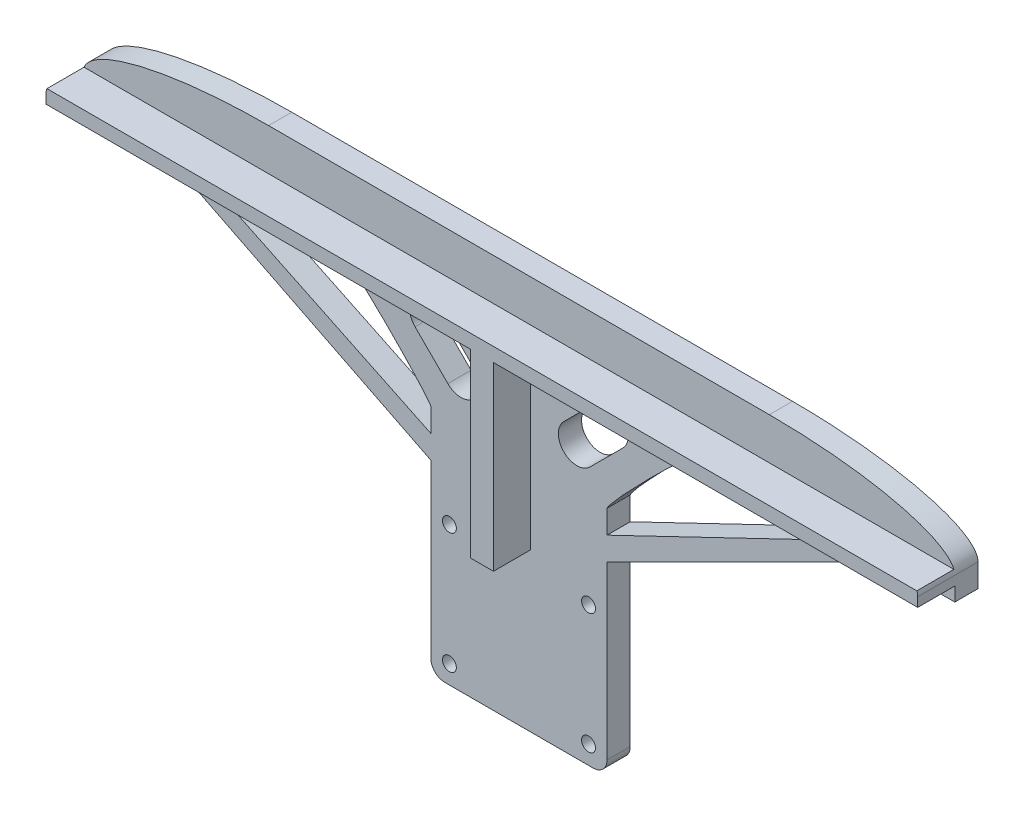
SolidWorks part; units mm, degrees
ref_plane "Front" through (0, 0, 0) normal (0, 0, 1) x (1, 0, 0)
ref_plane "Top" through (0, 0, 0) normal (0, 1, 0) x (1, 0, 0)
ref_plane "Right" through (0, 0, 0) normal (1, 0, 0) x (0, 0, -1)
sketch "Sketch1" plane through (0, 0, 0) normal (0, 0, 1) x (1, 0, 0)
  line L0 (38, 0) -> (113, 0)
  line L1 (0, 0) -> (38, 0)
  line L2 (0, 0) -> (0, -70)
  line L3 (0, -70) -> (38, -70)
  line L4 (38, 0) -> (38, -70)
  line L5 (113, 0) -> (113, 15)
  line L6 (113, 15) -> (-75, 15)
  line L7 (-75, 15) -> (-75, 0)
  line L8 (-75, 0) -> (0, 0)
  dimension "D1" = 38
  dimension "D2" = 70
  dimension "D3" = 75
  dimension "D4" = 75
  dimension "D5" = 15
extrude "Boss-Extrude1" add sketch "Sketch1" along normal blind 5 contours L4 L1 L2 L3 | L7 L8 L1 L0 L5 L6 region at (19, 7.5, 0) region at (19, -35, 0)
sketch "Sketch2" plane through (0, 0, 5) normal (0, 0, 1) x (1, 0, 0)
  line L0 (38, 0) -> (38, -70) construction
  line L1 (0, -70) -> (38, -70) construction
  circle A0 centre (34, -66) radius 1.5
  circle A1 centre (4, -66) radius 1.5
  circle A2 centre (4, -40) radius 1.5
  circle A3 centre (34, -40) radius 1.5
  dimension "D1" = 3
  dimension "D2" = 4
  dimension "D3" = 4
  dimension "D4" = 2
  dimension "D5" = 2
extrude "Cut-Extrude1" cut sketch "Sketch2" against normal through all
fillet "Fillet1" radius 3 2 edges at (38, -70, 2.5) (0, -70, 2.5)
fillet "Fillet2" radius 20 2 edges at (0, 0, 2.5) (38, 0, 2.5) conic rho 0.05
sketch "Sketch3" plane through (0, 0, 5) normal (0, 0, 1) x (1, 0, 0)
  line L0 (-75, 15) -> (-75, 0) construction
  line L1 (-75, 3) -> (113, 3)
  line L2 (-75, 3) -> (-75, 6)
  line L3 (-75, 6) -> (113, 6)
  line L4 (113, 3) -> (113, 6)
  line L5 (113, 0) -> (113, 15) construction
  dimension "D1" = 3
  dimension "D2" = 12
extrude "Boss-Extrude2" add sketch "Sketch3" along normal blind 8
sketch "Sketch4" plane through (0, 0, 5) normal (0, 0, 1) x (1, 0, 0)
  line L0 (-75, 3) -> (113, 3) construction
  line L1 (16.5, 3) -> (21.5, 3)
  line L2 (16.5, 3) -> (16.5, -36)
  line L3 (16.5, -36) -> (21.5, -36)
  line L4 (21.5, 3) -> (21.5, -36)
  line L5 (0, -20) -> (0, -67) construction
  dimension "D1" = 39
  dimension "D2" = 5
  dimension "D3" = 16.5
extrude "Boss-Extrude3" add sketch "Sketch4" along normal blind 8
sketch "Sketch5" plane through (0, 0, 5) normal (0, 0, 1) x (1, 0, 0)
  line L0 (90, 0) -> (38, -25)
  line L1 (58, 0) -> (113, 0) construction
  line L2 (38, -20) -> (38, -67) construction
  line L3 (38, -25) -> (38, -30)
  line L4 (38, -30) -> (98, 0)
  line L5 (98, 0) -> (90, 0)
  line L6 (-57.903, 0) -> (-52, 0)
  line L7 (-75, 0) -> (-20, 0) construction
  line L8 (-52, 0) -> (0, -25)
  line L9 (0, -20) -> (0, -67) construction
  line L10 (0, -25) -> (0, -30)
  line L11 (0, -30) -> (-60, 0)
  line L12 (-60, 0) -> (-52, 0)
  line L13 (-52, 0) -> (-52.0215, 0.2507)
  line L14 (113, 0) -> (113, 3) construction
  line L15 (-75, 3) -> (-75, 0) construction
  line M12 (-75, 0) -> (-20, 0)
  line M14 (0, -20) -> (0, -67)
  dimension "D1" = 15
  dimension "D2" = 8
  dimension "D3" = 5
  dimension "D4" = 5
  dimension "D5" = 5
  dimension "D6" = 5
  dimension "D7" = 15
  dimension "D8" = 8
extrude "Boss-Extrude4" add sketch "Sketch5" against normal blind 5 contours L11 L8 M14 M12 | L4 L5 L0 L3 region at (-26.9333, -14.3333, 5)
fillet "Fillet3" radius 40 1 edges at (-75, 15, 2.5) second distance 10 first distance on face at (19, 15, 2.5)
fillet "Fillet4" radius 10 1 edges at (113, 15, 2.5) second distance 40 first distance on face at (113, 6, 5.75)
sketch "Sketch6" plane through (0, 0, 5) normal (0, 0, 1) x (1, 0, 0)
  line L0 (6.5, -11.034) -> (-0.5711, -3.9629) construction
  line L1 (3.6716, -13.8624) -> (-3.3995, -6.7913)
  line L2 (9.3284, -8.2056) -> (2.2574, -1.1345)
  line L3 (31.5, -11.2734) -> (38.5711, -4.2024) construction
  line L4 (28.6716, -8.445) -> (35.7426, -1.3739)
  line L5 (34.3284, -14.1019) -> (41.3995, -7.0308)
  line L6 (16.5, 3) -> (16.5, -36) construction
  line L7 (21.5, -36) -> (21.5, 3) construction
  arc A0 (3.6716, -13.8624) -> (9.3284, -8.2056) centre (6.5, -11.034) ccw
  arc A1 (2.2574, -1.1345) -> (-3.3995, -6.7913) centre (-0.5711, -3.9629) ccw
  arc A2 (28.6716, -8.445) -> (34.3284, -14.1019) centre (31.5, -11.2734) ccw
  arc A3 (41.3995, -7.0308) -> (35.7426, -1.3739) centre (38.5711, -4.2024) ccw
  point P2 (2.9645, -7.4984)
  point P7 (35.0355, -7.7379)
  dimension "D1" = 4
  dimension "D2" = 4
  dimension "D3" = 10
  dimension "D4" = 10
  dimension "D5" = 10
  dimension "D6" = 10
extrude "Cut-Extrude2" cut sketch "Sketch6" against normal through all
